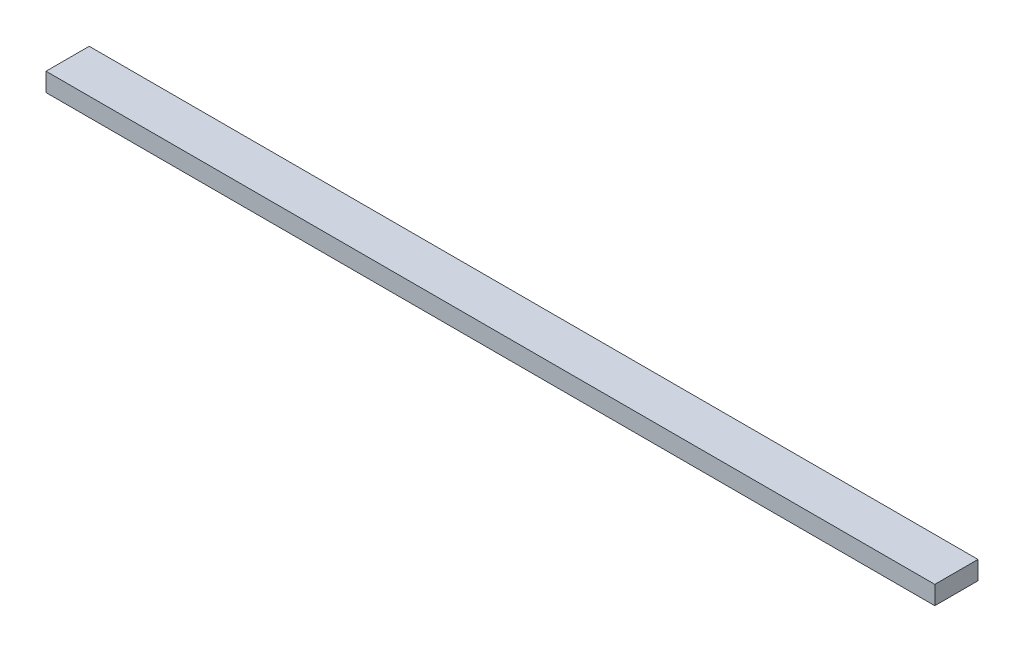
SolidWorks part; units mm, degrees
ref_plane "Front Plane" through (0, 0, 0) normal (0, 0, 1) x (1, 0, 0)
ref_plane "Top Plane" through (0, 0, 0) normal (0, 1, 0) x (1, 0, 0)
ref_plane "Right Plane" through (0, 0, 0) normal (1, 0, 0) x (0, 0, -1)
sketch "Sketch1" plane through (0, 0, 0) normal (0, 1, 0) x (1, 0, 0)
  line L0 (1828.8, 88.9) -> (1828.8, 0)
  line L1 (0, 0) -> (1828.8, 0)
  line L2 (0, 0) -> (0, 88.9)
  line L3 (0, 88.9) -> (1828.8, 88.9)
  line L5 (1568.45, 88.9) -> (1568.45, 0) construction
  line L6 (1479.55, 88.9) -> (1479.55, 0) construction
  line L7 (1390.65, 88.9) -> (1390.65, 0) construction
  line L8 (1301.75, 88.9) -> (1301.75, 0) construction
  line L9 (1212.85, 88.9) -> (1212.85, 0) construction
  line L10 (1123.95, 88.9) -> (1123.95, 0) construction
  line L11 (1035.05, 88.9) -> (1035.05, 0) construction
  line L12 (946.15, 88.9) -> (946.15, 0) construction
  line L13 (857.25, 88.9) -> (857.25, 0) construction
  line L14 (768.35, 88.9) -> (768.35, 0) construction
  line L15 (679.45, 88.9) -> (679.45, 0) construction
  line L16 (590.55, 88.9) -> (590.55, 0) construction
  line L17 (501.65, 88.9) -> (501.65, 0) construction
  line L18 (412.75, 88.9) -> (412.75, 0) construction
  line L19 (323.85, 88.9) -> (323.85, 0) construction
  line L20 (234.95, 88.9) -> (234.95, 0) construction
  line L21 (146.05, 88.9) -> (146.05, 0) construction
  line L22 (146.05, 88.9) -> (146.05, 0) [skipped]
  dimension "D1" = 88.9
  dimension "D2" = 1828.8
  dimension "D3" = 90
  dimension "D4" = 17
  dimension "D5" = 260.35
  dimension "D6" = 349.25
  dimension "D7" = 438.15
  dimension "D8" = 527.05
  dimension "D9" = 615.95
  dimension "D10" = 704.85
  dimension "D11" = 793.75
  dimension "D12" = 882.65
  dimension "D13" = 971.55
  dimension "D14" = 88.9
  dimension "D15" = 1060.45
  dimension "D16" = 1149.35
  dimension "D17" = 1238.25
  dimension "D18" = 1327.15
  dimension "D19" = 1422.4
  dimension "D20" = 1593.85
extrude "Boss-Extrude1" add sketch "Sketch1" against normal blind 38.1
